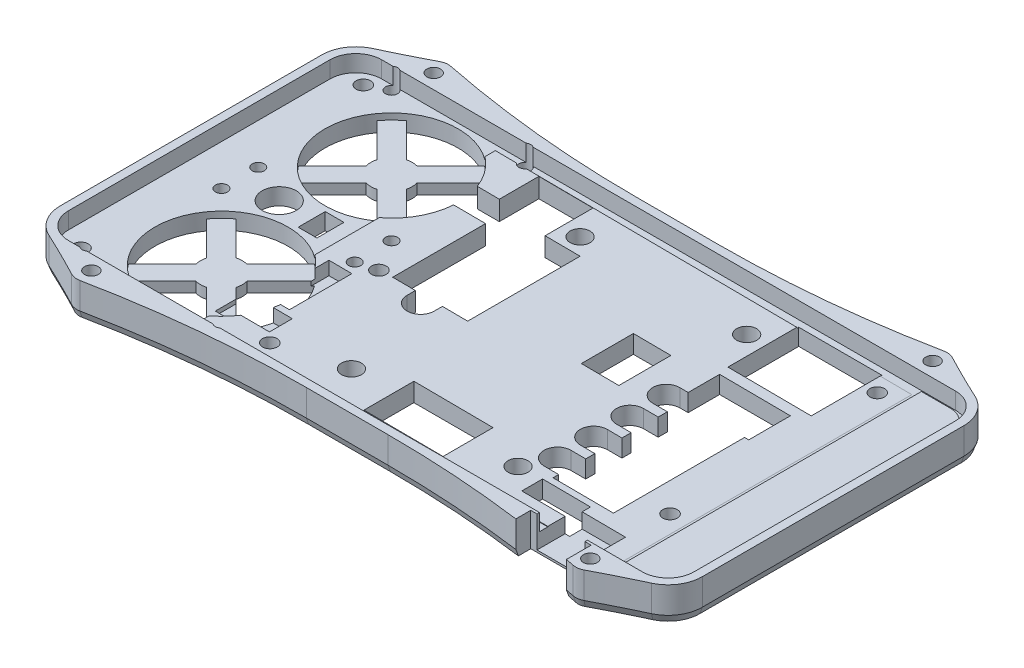
SolidWorks part; units mm, degrees
ref_plane "前视基准面" through (0, 0, 0) normal (0, 0, 1) x (1, 0, 0)
ref_plane "上视基准面" through (0, 0, 0) normal (0, 1, 0) x (1, 0, 0)
ref_plane "右视基准面" through (0, 0, 0) normal (1, 0, 0) x (0, 0, -1)
sketch "草图1" plane through (0, 0, 0) normal (0, 1, 0) x (1, 0, 0)
  line L0 (6, 0.2) -> (143.8, 0.2)
  line L1 (6, 0) -> (143.8, 0) construction
  line L2 (0, -6) -> (0, -68.8) construction
  line L3 (6, -74.8) -> (143.8, -74.8) construction
  line L4 (149.8, -6) -> (149.8, -68.8) construction
  line L5 (150, -6) -> (150, -68.8)
  line L6 (6, -75) -> (143.8, -75)
  line L7 (-0.2, -6) -> (-0.2, -68.8)
  arc A0 (143.8, 0) -> (149.8, -6) centre (143.8, -6) cw construction
  arc A1 (143.8, -74.8) -> (149.8, -68.8) centre (143.8, -68.8) ccw construction
  arc A2 (0, -68.8) -> (6, -74.8) centre (6, -68.8) ccw construction
  arc A3 (6, 0) -> (0, -6) centre (6, -6) ccw construction
  arc A4 (143.8, 0.2) -> (150, -6) centre (143.8, -6) cw
  arc A5 (143.8, -75) -> (150, -68.8) centre (143.8, -68.8) ccw
  arc A6 (-0.2, -68.8) -> (6, -75) centre (6, -68.8) ccw
  arc A7 (6, 0.2) -> (-0.2, -6) centre (6, -6) ccw
  point P7 (149.8, 0)
  point P12 (0, -74.8)
  point P15 (0, 0)
  dimension "D3" = 6
  dimension "D1" = 74.8
  dimension "D2" = 149.8
  dimension "D4" = 0.2
extrude "凸台-拉伸1" add sketch "草图1" along normal blind 4
sketch "草图2" plane through (0, 0, 0) normal (0, -1, 0) x (-1, 0, 0)
  line L0 (-122.6, -55.35) -> (-108.9, -55.35)
  line L1 (-122.6, -69.85) -> (-108.9, -69.85)
  line L2 (-122.6, -69.85) -> (-122.6, -63.95)
  line L3 (-122.6, -63.95) -> (-108.9, -63.95)
  line L4 (-108.9, -69.85) -> (-108.9, -63.95)
  line L5 (-135.3, -1.25) -> (-35.3, -1.25) construction
  line L6 (-135.3, -1.25) -> (-135.3, -73.55) construction
  line L7 (-135.3, -73.55) -> (-35.3, -73.55) construction
  line L8 (-35.3, -1.25) -> (-35.3, -73.55) construction
  line L9 (-108.9, -61.25) -> (-108.9, -55.35)
  line L10 (-122.6, -61.25) -> (-108.9, -61.25)
  line L11 (-122.6, -61.25) -> (-122.6, -55.35)
  line L12 (-122.6, -46.75) -> (-108.9, -46.75)
  line L13 (-108.9, -52.65) -> (-108.9, -46.75)
  line L14 (-122.6, -52.65) -> (-108.9, -52.65)
  line L15 (-122.6, -52.65) -> (-122.6, -46.75)
  line L16 (-122.6, -38.15) -> (-108.9, -38.15)
  line L17 (-108.9, -44.05) -> (-108.9, -38.15)
  line L18 (-122.6, -44.05) -> (-108.9, -44.05)
  line L19 (-122.6, -44.05) -> (-122.6, -38.15)
  line L20 (0, -6) -> (0, -68.8) construction
  line L21 (-35.3, -73.55) -> (-0.8, -73.55) construction
  line L22 (-120.25, -26.65) -> (-111.25, -26.65) construction
  line L23 (-120.25, -26.65) -> (-120.25, -33.15) construction
  line L24 (-120.25, -33.15) -> (-111.25, -33.15) construction
  line L25 (-111.25, -26.65) -> (-111.25, -33.15) construction
  line L26 (-85.8, -48.75) -> (-81.1, -48.75) construction
  line L27 (-85.8, -48.75) -> (-85.8, -58.15) construction
  line L28 (-85.8, -58.15) -> (-81.1, -58.15) construction
  line L29 (-81.1, -48.75) -> (-81.1, -58.15) construction
  line L30 (-71.5, -48.65) -> (-68.2, -48.65) construction
  line L31 (-71.5, -48.65) -> (-71.5, -57.55) construction
  line L32 (-71.5, -57.55) -> (-68.2, -57.55) construction
  line L33 (-68.2, -48.65) -> (-68.2, -57.55) construction
  line L34 (-43.1, -45.05) -> (-38.6, -45.05) construction
  line L35 (-43.1, -45.05) -> (-43.1, -59.05) construction
  line L36 (-43.1, -59.05) -> (-38.6, -59.05) construction
  line L37 (-38.6, -45.05) -> (-38.6, -59.05) construction
  line L38 (-45.3, -61.55) -> (-33.3, -61.55) construction
  line L39 (-45.3, -61.55) -> (-45.3, -66.05) construction
  line L40 (-45.3, -66.05) -> (-33.3, -66.05) construction
  line L41 (-33.3, -61.55) -> (-33.3, -66.05) construction
  line L42 (-0.8, -73.55) -> (-0.8, -1.25) construction
  line L43 (-0.8, -1.25) -> (-35.3, -1.25) construction
  line L44 (-149.8, -6) -> (-149.8, -68.8) construction
  line L45 (-30.8, -34.65) -> (-27.3, -34.65) construction
  line L46 (-30.8, -34.65) -> (-30.8, -40.15) construction
  line L47 (-30.8, -40.15) -> (-27.3, -40.15) construction
  line L48 (-27.3, -34.65) -> (-27.3, -40.15) construction
  line L49 (-120.75, -33.65) -> (-110.75, -33.65)
  line L50 (-110.75, -26.15) -> (-110.75, -33.65)
  line L51 (-120.75, -26.15) -> (-110.75, -26.15)
  line L52 (-120.75, -26.15) -> (-120.75, -33.65)
  line L53 (-86.3, -48.25) -> (-86.3, -58.65)
  line L54 (-86.3, -58.65) -> (-80.6, -58.65)
  line L55 (-80.6, -48.25) -> (-80.6, -58.65)
  line L56 (-86.3, -48.25) -> (-80.6, -48.25)
  line L57 (-72, -48.15) -> (-72, -58.05)
  line L58 (-72, -58.05) -> (-67.7, -58.05)
  line L59 (-67.7, -48.15) -> (-67.7, -58.05)
  line L60 (-72, -48.15) -> (-67.7, -48.15)
  line L61 (-31.3, -34.15) -> (-31.3, -40.65)
  line L62 (-31.3, -40.65) -> (-26.8, -40.65)
  line L63 (-26.8, -34.15) -> (-26.8, -40.65)
  line L64 (-31.3, -34.15) -> (-26.8, -34.15)
  line L65 (-43.6, -44.55) -> (-43.6, -59.55)
  line L66 (-43.6, -59.55) -> (-38.1, -59.55)
  line L67 (-38.1, -44.55) -> (-38.1, -59.55)
  line L68 (-43.6, -44.55) -> (-38.1, -44.55)
  line L69 (-45.8, -61.05) -> (-45.8, -66.55)
  line L70 (-45.8, -66.55) -> (-32.8, -66.55)
  line L71 (-32.8, -61.05) -> (-32.8, -66.55)
  line L72 (-45.8, -61.05) -> (-32.8, -61.05)
  circle A0 centre (-103.2, -9.35) radius 2 construction
  circle A1 centre (-103.2, -64.25) radius 2 construction
  circle A2 centre (-63.2, -64.25) radius 2 construction
  circle A3 centre (-63.2, -9.35) radius 2 construction
  circle A4 centre (-130.8, -5.6) radius 1.25 construction
  circle A5 centre (-131.1, -55.65) radius 1.25 construction
  circle A6 centre (-47.7, -4.85) radius 1.25 construction
  circle A7 centre (-48.1, -68.75) radius 1.25 construction
  circle A8 centre (-22.8, -70.3) radius 1.25 construction
  circle A9 centre (-5.05, -71.05) radius 1.25 construction
  circle A10 centre (-5.05, -3.25) radius 1.25 construction
  circle A11 centre (-19, -37.4) radius 3.6 construction
  circle A12 centre (-103.2, -9.35) radius 2.4
  circle A13 centre (-63.2, -9.35) radius 2.4
  circle A14 centre (-63.2, -64.25) radius 2.4
  circle A15 centre (-103.2, -64.25) radius 2.4
  circle A16 centre (-19, -37.4) radius 4.1
  circle A17 centre (-130.8, -5.6) radius 1.75
  circle A18 centre (-131.1, -55.65) radius 1.75
  circle A19 centre (-48.1, -68.75) radius 1.75
  circle A20 centre (-22.8, -70.3) radius 1.75
  circle A21 centre (-5.05, -71.05) radius 1.75
  circle A22 centre (-5.05, -3.25) radius 1.75
  circle A23 centre (-47.7, -4.85) radius 1.75
  circle A24 centre (-46.11, -40.57) radius 1.25 construction
  circle A25 centre (-46.11, -40.57) radius 1.75
  point P22 (0, -37.4)
  point P23 (-135.3, -37.4)
  point P28 (-115.75, -33.15)
  point P29 (-115.75, -38.15)
  point P30 (-111.25, -29.9)
  point P31 (-108.9, -41.1)
  point P79 (-0.8, -37.4)
  point P81 (-27.3, -37.4)
  dimension "D21" = 4
  dimension "D34" = 2.5
  dimension "D53" = 7.2
  dimension "D1" = 13.7
  dimension "D2" = 5.9
  dimension "D3" = 72.3
  dimension "D4" = 3.7
  dimension "D5" = 12.7
  dimension "D7" = 14.5
  dimension "D8" = 100
  dimension "D9" = 2.7
  dimension "D10" = 9
  dimension "D11" = 6.5
  dimension "D12" = 11.2
  dimension "D13" = 15.4
  dimension "D14" = 9.4
  dimension "D15" = 4.7
  dimension "D16" = 23.1
  dimension "D17" = 3.3
  dimension "D18" = 8.9
  dimension "D19" = 16
  dimension "D20" = 37.4
  dimension "D22" = 8.1
  dimension "D23" = 32.1
  dimension "D24" = 40
  dimension "D25" = 9.3
  dimension "D26" = 14
  dimension "D27" = 4.5
  dimension "D28" = 12
  dimension "D29" = 4.5
  dimension "D30" = 3.3
  dimension "D31" = 2
  dimension "D32" = 7.5
  dimension "D33" = 14.5
  dimension "D35" = 34.5
  dimension "D36" = 2
  dimension "D37" = 4.25
  dimension "D38" = 2.5
  dimension "D39" = 3.25
  dimension "D40" = 22
  dimension "D41" = 4.8
  dimension "D42" = 12.8
  dimension "D43" = 3.6
  dimension "D44" = 12.4
  dimension "D45" = 4.35
  dimension "D46" = 4.5
  dimension "D47" = 4.2
  dimension "D48" = 17.9
  dimension "D49" = 18.2
  dimension "D50" = 3.5
  dimension "D51" = 5.5
  dimension "D52" = 8.3
  dimension "D58" = 28.18
  dimension "D59" = 1.99
  dimension "D54" = 0.4
  dimension "D55" = 0.5
  dimension "D56" = 0.5
  dimension "D57" = 0.5
  dimension "D6" = 4
sketch "草图7" plane through (0, 0, -0.2) normal (0, 0, -1) x (-1, 0, 0)
  line L0 (-135.3, 4) -> (-35.3, 4.75)
  line L2 (-35.3, 4.75) -> (-35.3, 4)
  line L4 (-35.3, 4) -> (-135.3, 4)
  line L6 (-143.8, 4) -> (-6, 4) construction
  dimension "D1" = 0.75
extrude "凸台-拉伸11" add sketch "草图7" against normal offset from surface (71.2 mm away) 2 from offset 2 up to face at (74.9, 2, 75) offset against normal yes
extrude "切除-拉伸1" cut sketch "草图2" against normal blind 10 contours A12 | A13 | A14 | A15
sketch "草图3" plane through (0, 0, 0) normal (0, 1, 0) x (1, 0, 0)
  line L0 (136.8, -1) -> (136.8, -73.8)
  line L1 (143.8, 0) -> (135.8, 0) construction
  line L2 (149.8, -6) -> (149.8, -68.8) construction
  line L3 (143.8, -74.8) -> (135.8, -74.8) construction
  line L4 (135.8, 0) -> (135.8, -74.8) construction
  line L5 (6, -74.8) -> (143.8, -74.8) construction
  line L6 (135.3, -1.25) -> (135.3, -73.55) construction
  line L7 (143.8, -73.8) -> (136.8, -73.8)
  line L8 (148.8, -6) -> (148.8, -68.8)
  line L9 (143.8, -1) -> (136.8, -1)
  arc A0 (143.8, 0) -> (149.8, -6) centre (143.8, -6) cw construction
  arc A1 (149.8, -68.8) -> (143.8, -74.8) centre (143.8, -68.8) cw construction
  arc A2 (148.8, -68.8) -> (143.8, -73.8) centre (143.8, -68.8) cw
  arc A3 (143.8, -1) -> (148.8, -6) centre (143.8, -6) cw
  point P17 (149.8, 0)
  dimension "D1" = 6
  dimension "D2" = 0.5
  dimension "D3" = 1
extrude "凸台-拉伸9" add sketch "草图3" along normal offset from surface (5 mm away) 1 up to face at (85.3, 4, 37.4) offset beyond the face yes
sketch "草图4" plane through (0, 0, 0) normal (0, 1, 0) x (1, 0, 0)
  line L0 (125.2, -20.85) -> (108.2, -20.85)
  line L1 (108.2, -30.85) -> (109.7, -30.85)
  line L2 (109.7, -30.85) -> (109.7, -62.35)
  line L3 (108.7, -68.85) -> (108.7, -62.35)
  line L4 (49.2, -40.35) -> (49.2, -13.35)
  line L5 (108.2, -30.85) -> (108.2, -20.85)
  line L6 (108.7, -68.85) -> (120.2, -68.85)
  line L7 (108.2, -30.85) -> (125.2, -30.85) construction
  line L8 (109.7, -62.35) -> (124.2, -62.35)
  line L9 (80.466, -18.85) -> (96.6871, -18.85) construction
  line L10 (107.2, 11.628) -> (107.2, 24.7853) construction
  line L11 (49.2, -13.35) -> (67.2, -13.35)
  line L12 (125.2, -30.85) -> (124.2, -30.85)
  line L13 (124.2, -30.85) -> (124.2, -62.35)
  line L14 (124.2, -62.35) -> (120.2, -62.35)
  line L15 (120.2, -62.35) -> (120.2, -68.85)
  line L16 (67.2, -13.35) -> (67.2, -40.35)
  line L17 (67.2, -40.35) -> (49.2, -40.35)
  line L18 (63.2, -9.35) -> (46.0308, -9.35) construction
  line L19 (106.2, -55.55) -> (106.2, -28.85) construction
  line L20 (108.7, -63.85) -> (120.2, -63.85)
  line L21 (125.2, -20.85) -> (125.2, -30.85)
  line L22 (106.2, -28.4) -> (108.2, -28.4)
  line L23 (106.2, -34.9) -> (109.7, -34.9)
  line L24 (106.2, -37.1) -> (109.7, -37.1)
  line L25 (109.7, -37.1) -> (109.7, -43.6)
  line L26 (109.7, -43.6) -> (106.2, -43.6)
  line L27 (106.2, -45.8) -> (109.7, -45.8)
  line L28 (106.2, -52.3) -> (109.7, -52.3)
  line L29 (106.2, -54.5) -> (109.7, -54.5)
  line L30 (106.2, -61) -> (109.7, -61)
  line L31 (54.65, -42.35) -> (54.65, -40.35)
  line L32 (61.15, -42.35) -> (61.15, -40.35)
  line L33 (89.5, -35.35) -> (89.5, -22.85)
  line L34 (89.5, -22.85) -> (98.5, -22.85)
  line L35 (98.5, -22.85) -> (98.5, -35.35)
  line L36 (98.5, -35.35) -> (89.5, -35.35)
  line L37 (58.8, -1.85) -> (58.8, -13.85)
  line L38 (58.8, -13.85) -> (45.8, -13.85)
  line L39 (107.7, -18.35) -> (107.7, -1.35)
  line L40 (107.7, -1.35) -> (127.7, -1.35)
  line L41 (127.7, -1.35) -> (127.7, -18.35)
  line L42 (127.7, -18.35) -> (107.7, -18.35)
  line L43 (92.2, -59.25) -> (92.2, -71.25)
  line L44 (92.2, -71.25) -> (73.2, -71.25)
  line L45 (73.2, -71.25) -> (73.2, -59.25)
  line L46 (73.2, -59.25) -> (92.2, -59.25)
  line L47 (45.8, -13.85) -> (45.8, -1.85)
  line L48 (45.8, -1.85) -> (58.8, -1.85)
  line L49 (45.8, -11.35) -> (39.8, -11.35)
  line L50 (39.8, -11.35) -> (39.8, -18.05)
  line L51 (39.8, -18.05) -> (45.8, -18.05)
  line L52 (45.8, -18.05) -> (45.8, -11.35)
  line L53 (45.8, -18.05) -> (49.2, -18.05)
  circle A0 centre (103.2, -9.35) radius 2.4 construction
  circle A1 centre (103.2, -64.25) radius 2.4 construction
  circle A2 centre (103.2, -64.25) radius 2.4
  circle A3 centre (63.2, -64.25) radius 2.4 construction
  circle A4 centre (63.2, -64.25) radius 2.4
  circle A5 centre (103.2, -9.35) radius 2.4 construction
  circle A6 centre (106.2, -31.65) radius 3.25
  circle A7 centre (106.2, -40.35) radius 3.25
  circle A8 centre (106.2, -49.05) radius 3.25
  circle A9 centre (106.2, -57.75) radius 3.25
  circle A10 centre (63.2, -9.35) radius 2.4 construction
  circle A11 centre (63.2, -9.35) radius 2.4 construction
  circle A12 centre (57.9, -42.35) radius 3.25
  point P30 (67.2, -26.85)
  dimension "D7" = 9.5
  dimension "D30" = 4.5
  dimension "D40" = 6.5
  dimension "D18" = 6.5
  dimension "D21" = 4.5
  dimension "D4" = 11.5
  dimension "D5" = 48
  dimension "D6" = 10
  dimension "D8" = 4
  dimension "D9" = 5
  dimension "D10" = 5
  dimension "D11" = 17
  dimension "D12" = 6.5
  dimension "D13" = 1
  dimension "D14" = 14
  dimension "D15" = 18
  dimension "D16" = 4
  dimension "D17" = 27
  dimension "D19" = 33
  dimension "D20" = 5.3
  dimension "D22" = 4.4
  dimension "D23" = 13
  dimension "D24" = 1.5
  dimension "D25" = 12.5
  dimension "D26" = 5.5
  dimension "D27" = 9
  dimension "D28" = 8.7
  dimension "D29" = 12
  dimension "D31" = 20
  dimension "D32" = 9
  dimension "D33" = 17
  dimension "D34" = 11
  dimension "D35" = 19
  dimension "D36" = 12
  dimension "D37" = 7
  dimension "D38" = 11.5
  dimension "D39" = 22.3
  dimension "D41" = 3
  dimension "D43" = 13.5
  dimension "D44" = 4.7
  dimension "D45" = 6
  dimension "D46" = 2.5
  dimension "D47" = 6.7
  dimension "D42" = 4
extrude "拉伸-薄壁1" add sketch "草图1<2>" along normal blind 8 thin thin type one direction wall 2
sketch "草图1<2>" plane through (0, 0, 0) normal (0, 1, 0) x (1, 0, 0) same geometry as "草图1"
extrude "切除-拉伸2" cut sketch "草图4" along normal through all contours L20 L3 L6 L15 | A9 L30 L2 L29 | A8 L28 L2 L27 | A7 L26 L2 L24 | A6 L23 L2 L1 | A6 L5 L22 | A12 L17 L31 | A12 L32 L17 | L52 L53 L4 L38 | L41 L42 L39 L40 | L8 L2 L1 L5 L0 L21 L12 L13 | A6 | A7 | A8 | A9 | L46 L43 L44 L45 | L35 L36 L33 L34 | L4 L11 L16 L17 | A12 | L47 L48 L37 L38 | L50 L51 L52 L49 region at (114.45, 0, 66.35) region at (107.7112, 0, 28.6021) region at (108.9903, 0, 33.7511) region at (109.6262, 0, 40.35) region at (107.95, 0, 60.9262) region at (109.6262, 0, 49.05) region at (47.5, 0, 15.95) region at (54.8521, 0, 40.8388) region at (60.9479, 0, 40.8388)
extrude "切除-拉伸3" cut sketch "草图2<11>" against normal through all contours L61 L62 L63 L64 | A16
sketch "草图2<11>" plane through (0, 0, 0) normal (0, -1, 0) x (-1, 0, 0) same geometry as "草图2"
extrude "切除-拉伸4" cut sketch "草图2<13>" against normal through all contours A17 | A18 | A19 | A23 | A22 | A21 | A25
sketch "草图2<13>" plane through (0, 0, 0) normal (0, -1, 0) x (-1, 0, 0) same geometry as "草图2"
extrude "切除-拉伸5" cut sketch "草图2<14>" against normal through all from offset 1.5 contours L67 L66 L65 L68 | L71 L70 L69 L72 offset against normal yes
sketch "草图2<14>" plane through (0, 0, 0) normal (0, -1, 0) x (-1, 0, 0) same geometry as "草图2"
sketch "草图5" plane through (0, 0, 0) normal (0, -1, 0) x (-1, 0, 0)
  text T0 "<b>M3*6</b>" font "@Adobe 黑体 Std R" height 7
  text T1 "<b>M3*6</b>" font "@Adobe 黑体 Std R" height 7
  text T2 "<b>M3*6</b>" font "@Adobe 黑体 Std R" height 7
  text T3 "<b>M3*6</b>" font "@Adobe 黑体 Std R" height 7
extrude "切除-拉伸6" [suppressed] cut sketch "草图5" against normal blind 0.6
sketch "草图6" plane through (0, 0, 0) normal (0, 1, 0) x (1, 0, 0)
  line L1 (0, -6) -> (0, -68.8) construction
  line L2 (149.8, -6) -> (149.8, -68.8) construction
  line L4 (6, 0.2) -> (143.8, 0.2) construction
  line L5 (6, -75) -> (143.8, -75) construction
  circle A0 centre (15, 3.7) radius 1.5 construction
  circle A1 centre (15, -78.5) radius 1.5 construction
  circle A2 centre (134.8, 3.7) radius 1.5 construction
  circle A3 centre (134.8, -78.5) radius 1.5 construction
  circle A4 centre (15, 3.7) radius 3.5
  circle A5 centre (15, -78.5) radius 3.5
  circle A6 centre (134.8, 3.7) radius 3.5
  circle A7 centre (134.8, -78.5) radius 3.5
  circle A8 centre (15, 3.7) radius 1.65
  circle A9 centre (134.8, 3.7) radius 1.65
  circle A10 centre (134.8, -78.5) radius 1.65
  circle A11 centre (15, -78.5) radius 1.65
  dimension "D1" = 3
  dimension "D3" = 0.15
  dimension "D4" = 15
  dimension "D5" = 15
  dimension "D2" = 2
extrude "凸台-拉伸10" add sketch "草图6" along normal up to surface (8 mm away) up to face at (74.9, 8, 37.4)
extrude "切除-拉伸9" cut sketch "草图6<2>" along normal through all contours A8 | A9 | A10 | A11
sketch "草图6<2>" plane through (0, 0, 0) normal (0, 1, 0) x (1, 0, 0) same geometry as "草图6"
fillet "圆角1" radius 250 8 edges at (18.1623, 4, 77) (11.8377, 4, 77) (131.6377, 4, 77) (137.9623, 4, 77) (137.9623, 4, -2.2) (131.6377, 4, -2.2) (11.8377, 4, -2.2) (18.1623, 4, -2.2)
chamfer "倒角1" distance 0.6 angle 70 20 edges at (40.2731, 0, 78.2358) (14.5029, 0, 81.9645) (74.9, 0, 77) (7.988, 0, 78.8506) (109.5269, 0, 78.2358) (-0.9143, 0, 73.2083) (135.2971, 0, 81.9645) (-2.2, 0, 37.4) (141.812, 0, 78.8506) (-0.9143, 0, 1.5917) (150.7143, 0, 73.2083) (7.988, 0, -4.0506) (152, 0, 37.4) (14.5029, 0, -7.1645) (150.7143, 0, 1.5917) (40.2731, 0, -3.4358) (141.812, 0, -4.0506) (74.9, 0, -2.2) (135.2971, 0, -7.1645) (109.5269, 0, -3.4358) first distance on face at (134.8, 0, 80.15)
sketch "草图8" plane through (0, 0, 0) normal (0, -1, 0) x (1, 0, 0)
  line L0 (9.5525, 32.9807) -> (9.5525, 0.9807) construction
  line L1 (9.5525, 0.9807) -> (41.5525, 0.9807) construction
  line L2 (41.5525, 0.9807) -> (41.5525, 32.9807) construction
  line L3 (41.5525, 32.9807) -> (9.5525, 32.9807) construction
  line L4 (31.3, 37.4) -> (26.8, 37.4) construction
  line L7 (41.5525, 41.8193) -> (9.5525, 41.8193) construction
  line L8 (41.5525, 73.8193) -> (41.5525, 41.8193) construction
  line L9 (9.5525, 73.8193) -> (41.5525, 73.8193) construction
  line L10 (9.5525, 41.8193) -> (9.5525, 73.8193) construction
  circle A0 centre (41.5525, 0.9807) radius 1.45
  circle A1 centre (41.5525, 32.9807) radius 1.45
  circle A2 centre (9.5525, 32.9807) radius 1.45
  circle A3 centre (9.5525, 0.9807) radius 1.45
  circle A4 centre (9.5525, 73.8193) radius 1.45
  circle A5 centre (9.5525, 41.8193) radius 1.45
  circle A6 centre (41.5525, 41.8193) radius 1.45
  circle A7 centre (41.5525, 73.8193) radius 1.45
  point P4 (9.5525, 16.9807)
  dimension "D3" = 2.9
  dimension "D4" = 2.9
  dimension "D5" = 2.9
  dimension "D6" = 2.9
  dimension "D1" = 32
  dimension "D2" = 32
extrude "切除-拉伸10" cut sketch "草图8" against normal through all
sketch "草图9" plane through (0, 0, 0) normal (0, -1, 0) x (1, 0, 0)
  line L0 (9.5525, 32.9807) -> (41.5525, 32.9807) construction
  line L1 (41.5525, 32.9807) -> (41.5525, 0.9807) construction
  line L2 (41.5525, 0.9807) -> (9.5525, 0.9807) construction
  line L3 (9.5525, 0.9807) -> (9.5525, 32.9807) construction
  line L4 (9.5525, 32.9807) -> (41.5525, 0.9807) construction
  line L5 (41.5525, 32.9807) -> (9.5525, 0.9807) construction
  line L6 (13.088, 32.9807) -> (41.5525, 4.5163)
  line L7 (41.5525, 4.5163) -> (38.017, 0.9807)
  line L8 (38.017, 0.9807) -> (9.5525, 29.4452)
  line L9 (9.5525, 29.4452) -> (13.088, 32.9807)
  line L10 (38.017, 32.9807) -> (9.5525, 4.5163)
  line L11 (9.5525, 4.5163) -> (13.088, 0.9807)
  line L12 (13.088, 0.9807) -> (41.5525, 29.4452)
  line L13 (41.5525, 29.4452) -> (38.017, 32.9807)
  line L14 (9.5525, 0.9807) -> (41.5525, 0.9807) construction
  line L15 (31.3, 37.4) -> (26.8, 37.4) construction
  line L18 (9.5525, 73.8193) -> (41.5525, 73.8193) construction
  line L19 (9.5525, 41.8193) -> (41.5525, 73.8193) construction
  line L20 (9.5525, 73.8193) -> (9.5525, 41.8193) construction
  line L21 (41.5525, 73.8193) -> (9.5525, 73.8193) construction
  line L22 (41.5525, 41.8193) -> (41.5525, 73.8193) construction
  line L23 (9.5525, 41.8193) -> (41.5525, 41.8193) construction
  line L24 (41.5525, 45.3548) -> (38.017, 41.8193)
  line L25 (13.088, 73.8193) -> (41.5525, 45.3548)
  line L26 (9.5525, 70.2837) -> (13.088, 73.8193)
  line L27 (38.017, 41.8193) -> (9.5525, 70.2837)
  line L28 (9.5525, 45.3548) -> (13.088, 41.8193)
  line L29 (38.017, 73.8193) -> (9.5525, 45.3548)
  line L30 (41.5525, 70.2837) -> (38.017, 73.8193)
  line L31 (13.088, 41.8193) -> (41.5525, 70.2837)
  line L32 (41.5525, 41.8193) -> (9.5525, 73.8193) construction
  circle A0 centre (25.5525, 16.9807) radius 16
  circle A1 centre (25.5525, 16.9807) radius 5
  circle A2 centre (25.5525, 57.8193) radius 5
  circle A3 centre (25.5525, 57.8193) radius 16
  dimension "D2" = 10
  dimension "D4" = 5
extrude "切除-拉伸11" cut sketch "草图9" against normal blind 10 contours A1 L10 A0 L6 | A1 L6 A0 L12 | A1 L12 A0 L8 | A1 L8 A0 L10 | A3 L29 A2 L27 | A3 L25 A2 L29 | A3 L31 A2 L25 | A3 L27 A2 L31 region at (25.5525, 0, 28.2322) region at (14.301, 0, 16.9807) region at (36.804, 0, 16.9807) region at (25.5525, 0, 5.7292) region at (36.804, 0, 57.8193) region at (25.5525, 0, 46.5678) region at (14.301, 0, 57.8193) region at (25.5525, 0, 69.0708)
sketch "草图10" plane through (0, 4, 0) normal (0, 1, 0) x (1, 0, 0)
  circle A0 centre (25.5525, -16.9807) radius 16
  circle A1 centre (25.5525, -57.8193) radius 16
  dimension "D1" = 32
  dimension "D2" = 32
extrude "切除-拉伸12" cut sketch "草图10" against normal mid plane 3
sketch "草图11" plane through (0, 8, 0) normal (0, 1, 0) x (1, 0, 0)
  line L0 (119.1, -85.85) -> (119.1, -65.85)
  line L1 (119.1, -65.85) -> (130.6, -65.85)
  line L2 (130.6, -65.85) -> (130.6, -85.85)
  line L3 (130.6, -85.85) -> (119.1, -85.85)
  line L4 (120.2, -63.85) -> (108.7, -63.85) construction
  circle A0 centre (131.1, -55.65) radius 1.75 construction
  circle A1 centre (131.1, -55.65) radius 1.75 construction
  dimension "D1" = 11.5
  dimension "D2" = 0.5
  dimension "D3" = 2
  dimension "D4" = 20
extrude "切除-拉伸13" cut sketch "草图11" against normal blind 4.5 from surface starting at face at (143.4785, 5, 37.4)
sketch "草图12" plane through (0, 8, 0) normal (0, 1, 0) x (1, 0, 0)
  line L0 (117.6, -75.6) -> (117.6, -88.4406)
  line L1 (117.6, -88.4406) -> (132.1, -88.4406)
  line L2 (132.1, -88.4406) -> (132.1, -75.6)
  line L3 (132.1, -75.6) -> (117.6, -75.6)
  line L4 (42.3942, -75) -> (143.8, -75) construction
  line L5 (119.1, -73) -> (119.1, -75) construction
  line L6 (130.6, -75) -> (130.6, -73) construction
  dimension "D1" = 0.6
  dimension "D2" = 1.5
  dimension "D3" = 1.5
extrude "切除-拉伸14" cut sketch "草图12" against normal through all
sketch "草图13" plane through (0, 0, 75.6) normal (0, 0, 1) x (1, 0, 0)
  line L0 (130.6, 5) -> (130.6, 8)
  line L1 (132.1, 8) -> (117.6, 8) construction
  line L2 (130.6, 8) -> (119.1, 8)
  line L3 (119.1, 8) -> (119.1, 5)
  line L4 (119.1, 5) -> (130.6, 5)
extrude "切除-拉伸15" cut sketch "草图13" against normal up to next
equation "\"D1@草图3\"=\"D3@草图1\""
